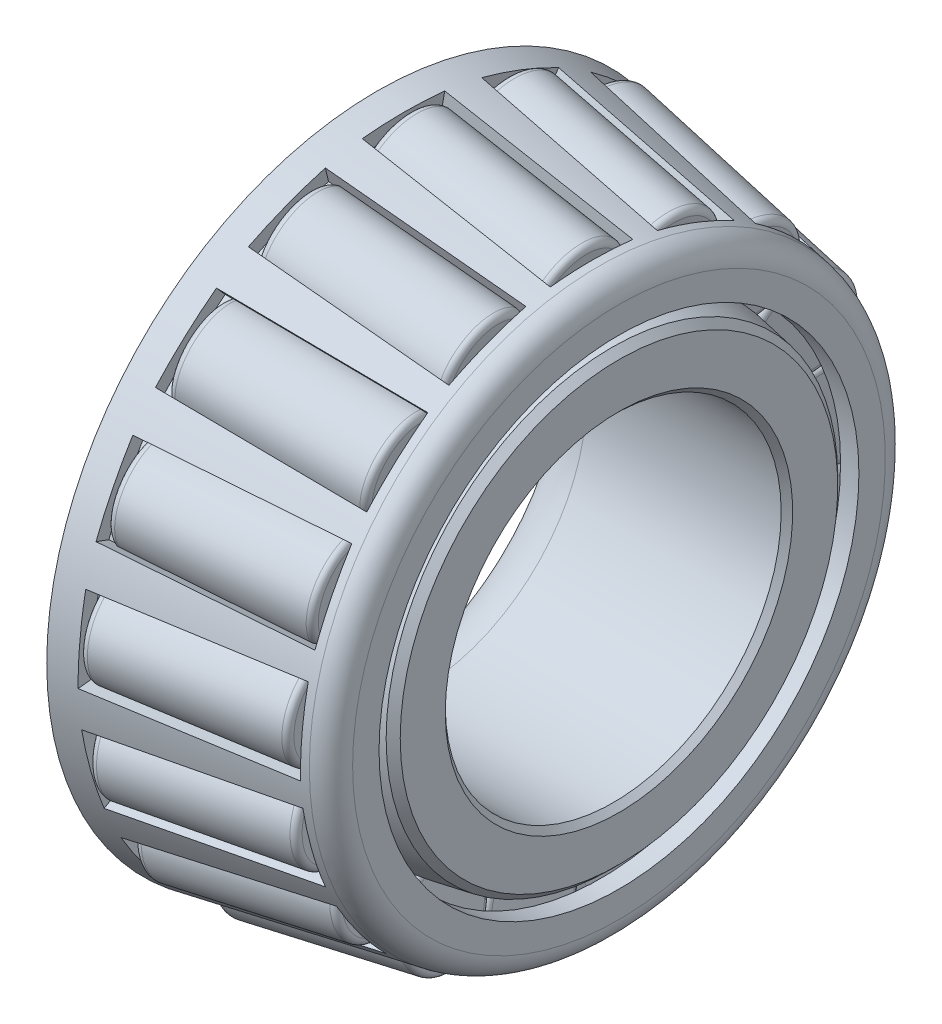
SolidWorks part; units mm, degrees
material "Alloy Steel"
ref_plane "Front" through (0, 0, 0) normal (0, 0, 1) x (1, 0, 0)
ref_plane "Top" through (0, 0, 0) normal (0, 1, 0) x (1, 0, 0)
ref_plane "Right" through (0, 0, 0) normal (1, 0, 0) x (0, 0, -1)
sketch "Sketch1" plane through (0, 0, 0) normal (0, 0, 1) x (1, 0, 0)
  line L0 (0, 22.0726) -> (0, 24.6126) construction
  line L1 (0, 24.6126) -> (12.7, 24.6126) construction
  line L2 (13.97, 23.3426) -> (13.97, 19.5326) construction
  line L3 (13.97, 19.5326) -> (0, 22.0726) construction
  line L4 (0, 0) -> (13.97, 0) construction
  line L5 (13.3037, 19.6537) -> (13.97, 20.32) construction
  line L6 (-1.651, 21.8565) -> (13.0475, 19.184)
  line L7 (14.351, 17.6221) -> (14.351, 15.875)
  line L8 (-1.651, 21.8565) -> (-1.651, 20.6431)
  line L9 (-1.651, 20.6431) -> (12.8144, 18.013)
  line L10 (13.1376, 17.6257) -> (13.1376, 15.875)
  line L11 (13.1376, 15.875) -> (14.351, 15.875)
  line L12 (14.351, 14.8532) -> (-2.794, 17.9705)
  line L13 (-2.794, 17.9705) -> (-2.794, 14.986)
  line L14 (1.0795, 11.1125) -> (14.351, 11.1125)
  line L15 (14.351, 11.1125) -> (14.351, 14.8532)
  line L16 (-2.794, 14.986) -> (13.6207, 14.986) construction
  arc A0 (12.7, 24.6126) -> (13.97, 23.3426) centre (12.7, 23.3426) cw construction
  arc A1 (13.0475, 19.184) -> (14.351, 17.6221) centre (12.7635, 17.6221) cw
  arc A2 (12.8144, 18.013) -> (13.1376, 17.6257) centre (12.7439, 17.6257) cw
  arc A3 (-2.794, 14.986) -> (1.0795, 11.1125) centre (1.0795, 14.986) ccw
  dimension "D1" = 1.27
  dimension "D12" = 1.5875
  dimension "D13" = 0.3937
  dimension "D17" = 6.858
  dimension "D2" = 13.97
  dimension "D3" = 4.7625
  dimension "D4" = 5.08
  dimension "D5" = 2.54
  dimension "D6" = 135
  dimension "D7" = 0.7874
  dimension "D8" = 0.508
  dimension "D10" = 1.1938
  dimension "D11" = 1.143
  dimension "D14" = 17.145
  dimension "D15" = 11.1125
  dimension "D16" = 13.5001
  dimension "D18" = 0.381
  dimension "D19" = 3.8735
sketch "Sketch2" plane through (0, 0, 0) normal (0, 0, 1) x (1, 0, 0)
  line L0 (13.97, 19.5326) -> (0, 22.0726) construction
  line L1 (12.2886, 19.8383) -> (0.5931, 21.9648) construction
  line L2 (14.351, 17.6221) -> (14.351, 15.875) construction
  line L3 (-1.651, 21.8565) -> (-1.651, 20.6431) construction
  line L4 (-1.651, 21.8565) -> (13.0475, 19.184) construction
  line L5 (14.351, 18.947) -> (14.351, 15.875) construction
  line L6 (-1.651, 21.8565) -> (-1.651, 20.6431) construction
  line L7 (-1.651, 21.8565) -> (14.351, 18.947) construction
  line L8 (6.35, 20.4017) -> (5.527, 15.875) construction
  line L9 (0.5931, 21.9648) -> (0.0252, 18.841) construction
  line L10 (12.2886, 19.8383) -> (11.7206, 16.7145) construction
  line L11 (0.0252, 18.841) -> (11.7206, 16.7145) construction
  line L12 (0.7863, 25.1567) -> (13.2314, 22.8939)
  line L13 (-0.3497, 18.9091) -> (0.7863, 25.1567)
  line L14 (12.0955, 16.6464) -> (13.2314, 22.8939)
  line L15 (-0.3497, 18.9091) -> (12.0955, 16.6464)
  dimension "D1" = 11.8872
  dimension "D2" = 3.175
  dimension "D4" = 0.381
  dimension "D3" = 6.35
sketch "Sketch3" plane through (0, 0, 0) normal (0, 0, 1) x (1, 0, 0)
  line L0 (-0.3497, 18.9091) -> (12.0955, 16.6464) construction
  line L1 (12.2886, 19.8383) -> (11.7206, 16.7145) construction
  line L2 (13.97, 19.5326) -> (0, 22.0726) construction
  line L3 (0.5931, 21.9648) -> (0.0252, 18.841) construction
  line L4 (0.0252, 18.841) -> (11.7206, 16.7145)
  line L5 (12.2886, 19.8383) -> (11.7206, 16.7145)
  line L6 (12.2886, 19.8383) -> (0.5931, 21.9648)
  line L7 (0.5931, 21.9648) -> (0.0252, 18.841)
revolve "Revolve1" add sketch "Sketch1" angle 360 about L4
extrude "Extrude2" cut sketch "Sketch2" against normal mid plane 5.461
pattern_circular "CirPattern1" count 17 over 360 about axis through (-1.651, 0, 0) along (1, 0, 0) of "Extrude2"
revolve "Revolve2" add sketch "Sketch1<5>" angle 360 about L4
sketch "Sketch1<5>" plane through (0, 0, 0) normal (0, 0, 1) x (1, 0, 0) same geometry as "Sketch1"
revolve "Revolve3" add sketch "Sketch3" angle 360 about L4
fillet "Fillet1" radius 0.4064 2 edges at (11.1527, 13.5907, 0) (-0.5428, 15.7172, 0)
pattern_circular "CirPattern2" count 17 over 360 about axis through (0, 0, 0) along (-1, 0, 0) of bodies 108
combine bodies "Combine1" operation type add bodies to combine 106 107 108 109 110 111 112 113 114 115 116 117 118 119 120 121 122 123 124
chamfer "Chamfer1" distance 0.381 angle 45 3 edges at (14.351, 0, 14.8532) (-2.794, 0, 17.9705) (14.351, 0, 11.1125) first distance on face at (14.351, 0, 14.8532) first distance on face at (5.6684, 16.264, 0.0014) first distance on face at (14.351, 0, 11.1125)
